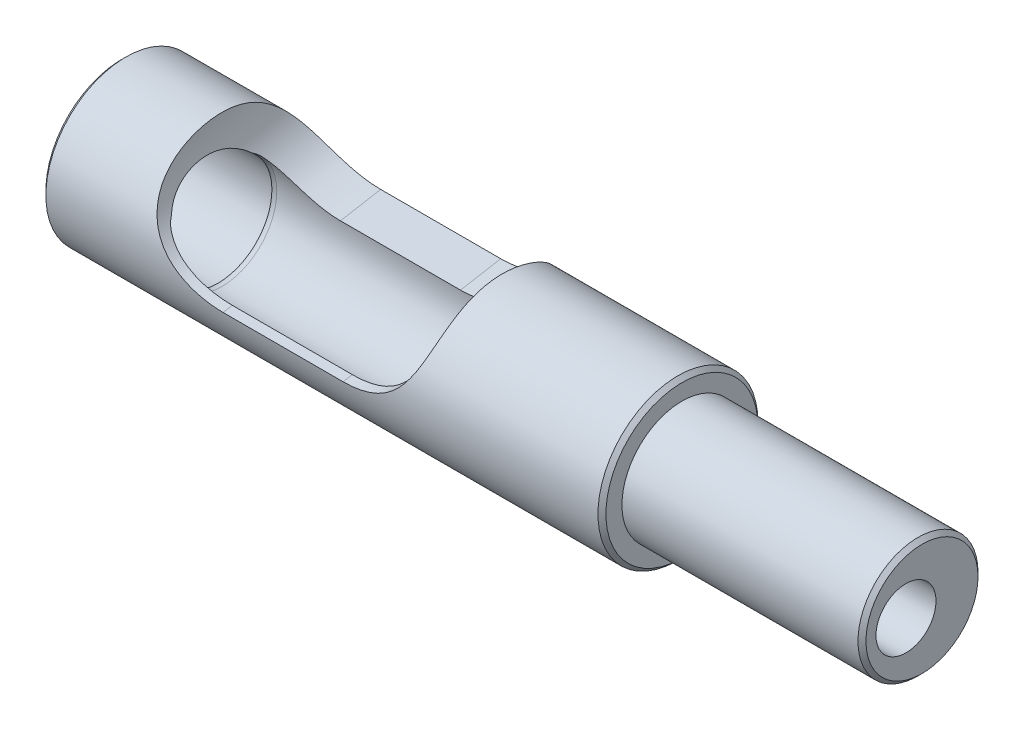
SolidWorks part; units mm, degrees
ref_plane "前视基准面" through (0, 0, 0) normal (0, 0, 1) x (1, 0, 0)
ref_plane "上视基准面" through (0, 0, 0) normal (0, 1, 0) x (1, 0, 0)
ref_plane "右视基准面" through (0, 0, 0) normal (1, 0, 0) x (0, 0, -1)
sketch "草图1" plane through (0, 0, 0) normal (1, 0, 0) x (0, 0, -1)
  circle A0 centre (0, 0) radius 20
  dimension "D1" = 40
extrude "凸台-拉伸1" add sketch "草图1" along normal blind 140
sketch "草图2" plane through (140, 0, 0) normal (1, 0, 0) x (0, 0, -1)
  circle A0 centre (0, 0) radius 15
  dimension "D1" = 30
extrude "凸台-拉伸2" add sketch "草图2" along normal blind 60
chamfer "倒角1" distance 1 angle 45 3 edges at (0, 0, -20) (140, 0, -20) (200, 0, -15)
sketch "草图3" plane through (0, 0, 0) normal (-1, 0, 0) x (0, 0, 1)
  line L0 (22, 0) -> (-22, 0) construction
  line L1 (0, -22) -> (0, 22) construction
  circle A0 centre (4, 0) radius 13.5
  dimension "D1" = 27
  dimension "D2" = 4
extrude "切除-拉伸1" cut sketch "草图3" against normal blind 28
sketch "草图4" plane through (28, 0, 0) normal (-1, 0, 0) x (0, 0, 1)
  circle A0 centre (4, 0) radius 13.75
  dimension "D1" = 27.5
extrude "切除-拉伸2" cut sketch "草图4" against normal blind 72
sketch "草图5" plane through (100, 0, 0) normal (-1, 0, 0) x (0, 0, 1)
  circle A0 centre (4, 0) radius 8
  dimension "D1" = 16
extrude "切除-拉伸3" cut sketch "草图5" against normal offset from surface (80 mm away) 20 up to face at (200, 0, -14)
sketch "草图6" plane through (180, 0, 0) normal (-1, 0, 0) x (0, 0, 1)
  circle A0 centre (4, 0) radius 7.5
  dimension "D1" = 15
extrude "切除-拉伸4" cut sketch "草图6" against normal through all
fillet "圆角1" radius 2 3 edges at (28, 0, 17.75) (100, 0, 17.75) (180, 0, -4)
ref_axis "基准轴1" through (210, 0, 0) along (-1, 0, 0)
ref_plane "基准面1" through (0, 0, 0) normal (0, -0.1736, 0.9848) x (-1, 0, 0)
sketch "草图8" plane through (0, 0, 0) normal (0, -0.1736, 0.9848) x (-1, 0, 0)
  line L0 (-139, -20) -> (-1, -20) construction
  line L1 (-75, 0) -> (-45, 0)
  line L3 (0, 22) -> (0, -22) construction
  arc A0 (-25, -20) -> (-45, 0) centre (-45, -20) ccw
  arc A1 (-75, 0) -> (-95, -20) centre (-75, -20) ccw
  point P10 (-33.2551, -35.355)
  point P11 (-7.3349, -26.9673)
  point P12 (-43.8022, 0)
  dimension "D1" = 40
  dimension "D2" = 40
  dimension "D3" = 70
  dimension "D4" = 25
extrude "切除-拉伸5" cut sketch "草图8" against normal through all and the other way through all
